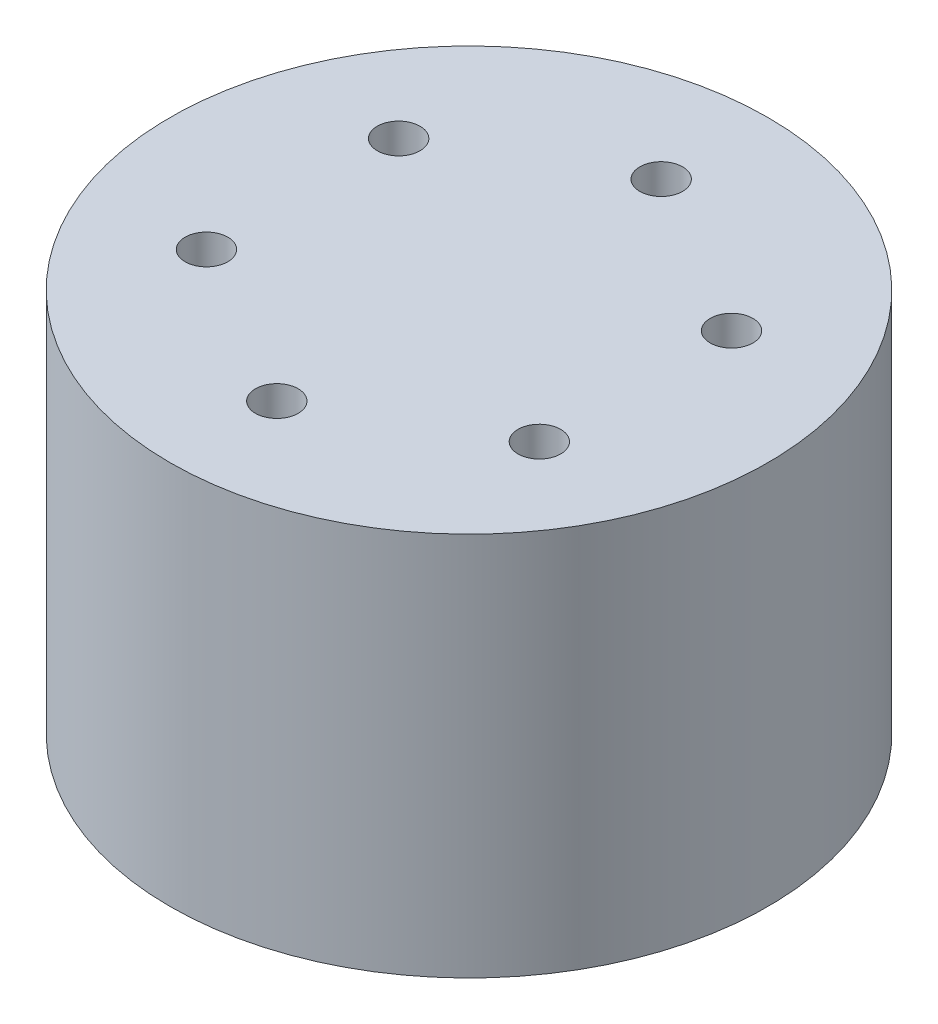
SolidWorks part; units mm, degrees
ref_plane "Front Plane" through (0, 0, 0) normal (0, 0, 1) x (1, 0, 0)
ref_plane "Top Plane" through (0, 0, 0) normal (0, 1, 0) x (1, 0, 0)
ref_plane "Right Plane" through (0, 0, 0) normal (1, 0, 0) x (0, 0, -1)
sketch "Sketch1" plane through (0, 0, 0) normal (0, 1, 0) x (1, 0, 0)
  circle A0 centre (0, 0) radius 35
  circle A1 centre (0, 0) radius 22.5 construction
  circle A2 centre (0, 0) radius 5
  circle A3 centre (0, 22.5) radius 2.5
  circle A4 centre (19.4856, 11.25) radius 2.5
  circle A5 centre (19.4856, -11.25) radius 2.5
  circle A6 centre (0, -22.5) radius 2.5
  circle A7 centre (-19.4856, -11.25) radius 2.5
  circle A8 centre (-19.4856, 11.25) radius 2.5
  point P19 (0, 0)
  dimension "D1" = 70
  dimension "D2" = 10
  dimension "D3" = 45
  dimension "D4" = 5
  dimension "D5" = 6
extrude "Boss-Extrude1" add sketch "Sketch1" along normal blind 45
sketch "Sketch2" plane through (0, 0, 0) normal (0, -1, 0) x (1, 0, 0)
  circle A0 centre (0, 0) radius 16
  dimension "D1" = 32
extrude "Cut-Extrude1" cut sketch "Sketch2" against normal blind 5
sketch "Sketch5" plane through (0, 45, 0) normal (0, 1, 0) x (1, 0, 0)
  circle A0 centre (0, 0) radius 13
  dimension "D1" = 26
extrude "Cut-Extrude2" cut sketch "Sketch5" against normal up to surface (40 mm away) up to face at (0, 5, -5)
sketch "Sketch6" plane through (0, 45, 0) normal (0, 1, 0) x (1, 0, 0)
  circle A0 centre (0, 0) radius 13
  circle A1 centre (0, 0) radius 13 construction
extrude "Boss-Extrude2" add sketch "Sketch6" against normal blind 18
